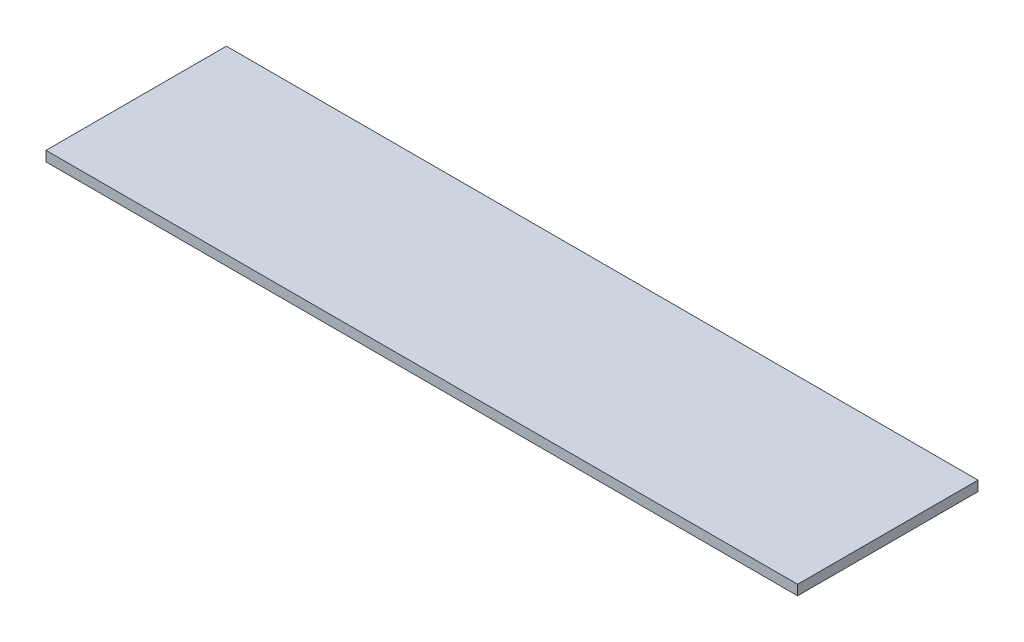
SolidWorks part; units mm, degrees
material "Liga 7079"
ref_plane "Plano frontal" through (0, 0, 0) normal (0, 0, 1) x (1, 0, 0)
ref_plane "Plano superior" through (0, 0, 0) normal (0, 1, 0) x (1, 0, 0)
ref_plane "Plano direito" through (0, 0, 0) normal (1, 0, 0) x (0, 0, -1)
sketch "Esboço1" plane through (0, 0, 0) normal (1, 0, 0) x (0, 0, -1)
  line L1 (-18, 0) -> (18, 0)
  dimension "D1" = 36
sheet metal parameters "Chapa metálica2" thickness 2 parameters "D1"=0.7366, "Espessura"=2
base flange "Flange-base2" sketch "Esboço1" end condition mid plane depth 150 reverse direction no thickness 2 reverse thickness direction no bend radius 0.7366
flat pattern "Padrão-Plano2" [suppressed]
sketch "Curva-Linhas2" plane through (0, 0, 0) normal (0, 1, 0) x (-1, 0, 0)
